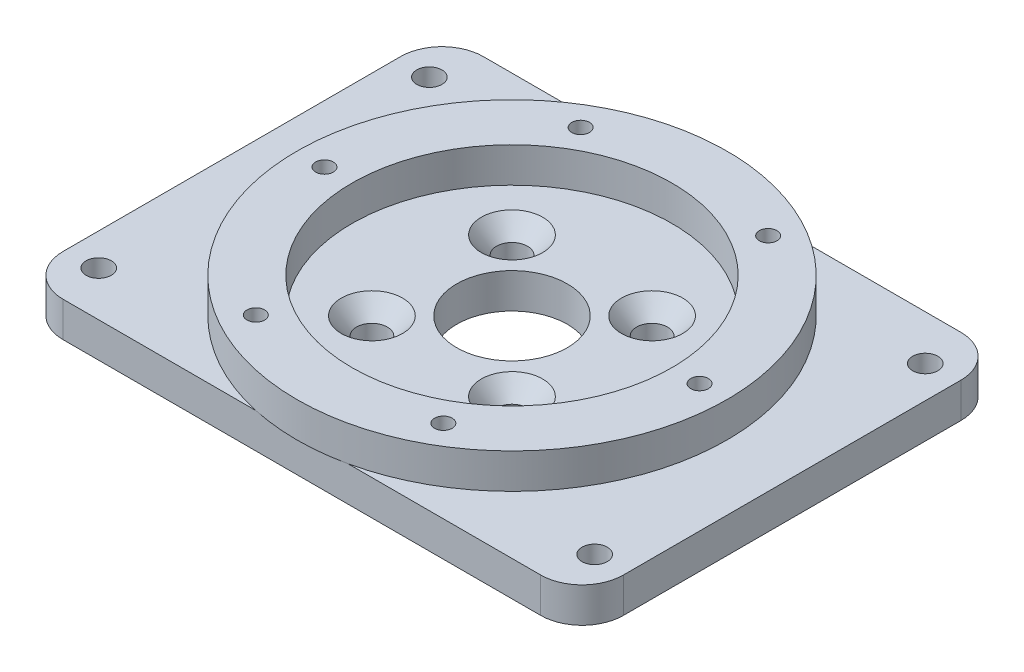
SolidWorks part; units mm, degrees
other "motorRingMount"
other "mainValvePlate"
ref_plane "Front Plane" through (0, 0, 0) normal (0, 0, 1) x (1, 0, 0)
ref_plane "Top Plane" through (0, 0, 0) normal (0, 1, 0) x (1, 0, 0)
ref_plane "Right Plane" through (0, 0, 0) normal (1, 0, 0) x (0, 0, -1)
sketch "Sketch1" plane through (0, 0, 0) normal (0, 1, 0) x (1, 0, 0)
  line L0 (0, 0) -> (0, -19.6757) construction
  line L6 (-50.8, -38.1) -> (50.8, -38.1)
  line L7 (0, 0) -> (-17, -29.4449) construction
  line L8 (0, 0) -> (-34, 0) construction
  line L9 (0, 0) -> (-17, 29.4449) construction
  line L10 (0, 0) -> (17, 29.4449) construction
  line L11 (0, 0) -> (34, 0) construction
  line L12 (0, 0) -> (17, -29.4449) construction
  line L13 (-50.8, -38.1) -> (-50.8, 38.1)
  line L14 (-50.8, 38.1) -> (50.8, 38.1)
  line L15 (50.8, -38.1) -> (50.8, 38.1)
  line L16 (-50.8, -38.1) -> (50.8, 38.1) construction
  line L17 (-50.8, 38.1) -> (50.8, -38.1) construction
  circle A0 centre (0, 0) radius 34 construction
  point P0 (0, 0)
  point P8 (0, -34)
  point P9 (44.958, -29.972)
  point P12 (-17, -29.4449)
  point P13 (-44.958, -29.972)
  point P20 (-44.958, 29.972)
  point P22 (44.958, 29.972)
  dimension "D1" = 68
  dimension "D2" = 76.2
  dimension "D3" = 101.6
  dimension "D4" = 30
  dimension "D5" = 6
  dimension "D6" = 44.958
  dimension "D7" = 29.972
extrude "Boss-Extrude1" add sketch "Sketch1" along normal blind 6.35
sketch "Sketch4" plane through (0, 0, 0) normal (0, -1, 0) x (1, 0, 0)
  circle A0 centre (-44.958, 29.972) radius 2.286
  circle A1 centre (-44.958, -29.972) radius 2.286
  circle A2 centre (44.958, -29.972) radius 2.286
  circle A3 centre (44.958, 29.972) radius 2.286
  circle A5 centre (0, 0) radius 10.033
  dimension "D1" = 4.572
  dimension "D2" = 20.066
extrude "Cut-Extrude1" cut sketch "Sketch4" against normal through all contours A0 | A1 | A2 | A3 | A5 region at (-44.958, 0, 29.972) region at (-44.958, 0, -29.972) region at (44.958, 0, -29.972) region at (44.958, 0, 29.972) region at (0, 0, 0)
sketch "Sketch6" plane through (0, 6.35, 0) normal (0, 1, 0) x (1, 0, 0)
  line L1 (-12.7, -12.7) -> (12.7, -12.7) construction
  line L2 (-12.7, -12.7) -> (-12.7, 12.7) construction
  line L3 (-12.7, 12.7) -> (12.7, 12.7) construction
  line L4 (12.7, -12.7) -> (12.7, 12.7) construction
  line L5 (-12.7, -12.7) -> (12.7, 12.7)
  line L6 (-12.7, 12.7) -> (12.7, -12.7)
  line L7 (0, 0) -> (0, 18.6441) construction
  line L8 (0, -41.91) -> (0, 41.91) construction
  point P0 (0, 0)
  point P1 (12.7, 12.7)
  point P2 (-12.7, -12.7)
  point P3 (-12.7, 12.7)
  point P4 (12.7, -12.7)
  dimension "D1" = 25.4
hole_wizard "CSK for #12 Flat Head Machine Screw3" positions "Sketch6" profile "Sketch10" countersink size "#12" standard "ANSI Inch" end condition up to next
sketch "Sketch10" plane through (12.7, 6.35, 12.7) normal (1, 0, 0) x (0, 0, 1)
  line L0 (0, 0) -> (0, 6.35)
  line L1 (0, 6.35) -> (2.8067, 6.35)
  line L2 (2.8067, 6.35) -> (2.8067, 3.1703)
  line L3 (2.8067, 3.1703) -> (5.5626, 0)
  line L5 (5.5626, 0) -> (0, 0)
  line L6 (-2.8067, 3.1703) -> (-5.5626, 0) construction
  line L11 (0, -6.35) -> (0, 107.95) construction
  dimension "Thru Hole Dia." = 5.6134
  dimension "Thru Hole Depth" = 6.35
  dimension "Near C'Sink Dia." = 11.1252
  dimension "Near C'Sink Angle" = 82
fillet "Fillet1" radius 7.5 4 edges at (50.8, 3.175, 38.1) (50.8, 3.175, -38.1) (-50.8, 3.175, -38.1) (-50.8, 3.175, 38.1)
sketch "Sketch12" plane through (0, 6.35, 0) normal (0, 1, 0) x (1, 0, 0)
  line L0 (34, 0) -> (39, 0) construction
  line L1 (34, 0) -> (29, 0) construction
  circle A0 centre (0, 0) radius 39
  circle A1 centre (0, 0) radius 29
  dimension "D1" = 5
extrude "Boss-Extrude3" add sketch "Sketch12" along normal blind 6.35 separate body
hole_wizard "CSK for M3 SFHCS1" positions "Sketch15" profile "Sketch16" countersink size "M3" standard "ANSI Metric" end condition through all
sketch "Sketch15" plane through (0, 0, 0) normal (0, -1, 0) x (-1, 0, 0)
  point P0 (-17, 29.4449)
  point P3 (-34, 0)
  point P6 (-17, -29.4449)
  point P9 (17, -29.4449)
  point P12 (34, 0)
  point P15 (17, 29.4449)
sketch "Sketch16" plane through (17, 0, -29.4449) normal (1, 0, 0) x (0, 0, -1)
  line L0 (0, 0) -> (0, 12.7)
  line L1 (0, 12.7) -> (1.6, 12.7)
  line L2 (1.6, 12.7) -> (1.6, 1.76)
  line L3 (1.6, 1.76) -> (3.36, 0)
  line L5 (3.36, 0) -> (0, 0)
  line L6 (-1.6, 1.76) -> (-3.36, 0) construction
  line L11 (0, -6.35) -> (0, 107.95) construction
  dimension "Thru Hole Dia." = 3.2
  dimension "Thru Hole Depth" = 12.7
  dimension "Near C'Sink Dia." = 6.72
  dimension "Near C'Sink Angle" = 90
